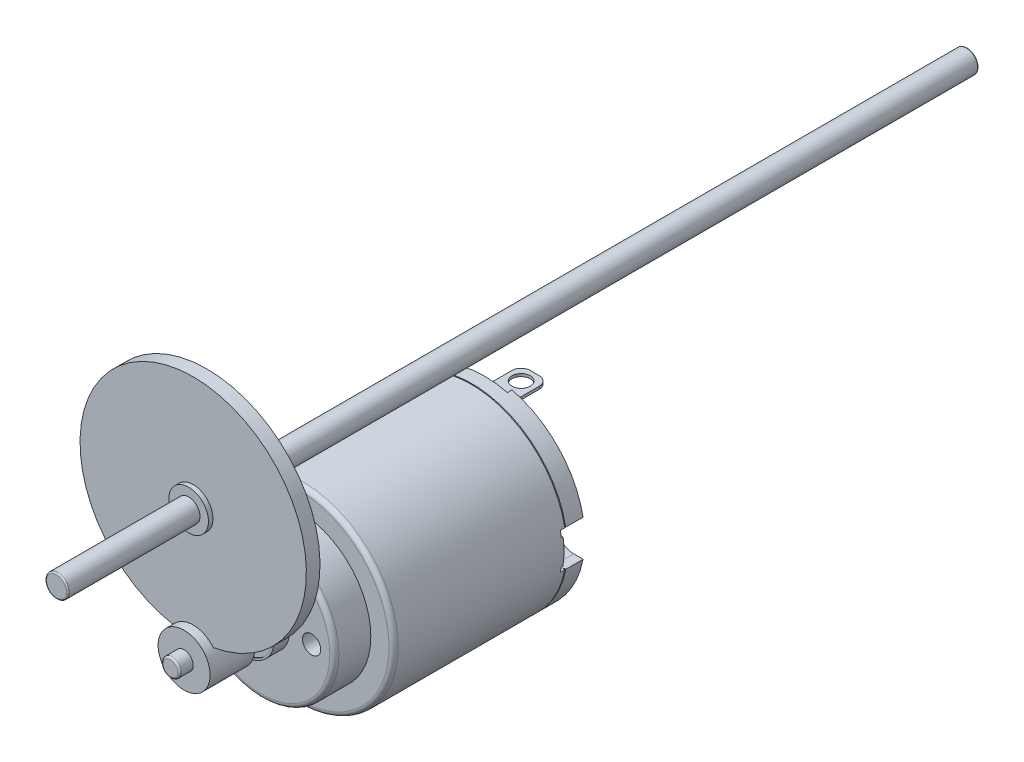
SolidWorks part; units mm, degrees
ref_plane "Plano frontal" through (0, 0, 0) normal (0, 0, 1) x (1, 0, 0)
ref_plane "Plano superior" through (0, 0, 0) normal (0, 1, 0) x (1, 0, 0)
ref_plane "Plano direito" through (0, 0, 0) normal (1, 0, 0) x (0, 0, -1)
sketch "Esboço1" plane through (0, 0, 0) normal (0, 0, 1) x (1, 0, 0)
  circle A0 centre (0, 0) radius 1
  dimension "D1" = 2
extrude "Ressalto-extrusão1" add sketch "Esboço1" along normal blind 38
ref_plane "Plano1" through (0, 0, 28) normal (0, 0, 1) x (1, 0, 0)
sketch "Esboço2" plane through (0, 0, 28) normal (0, 0, 1) x (1, 0, 0)
  circle A0 centre (0, 0) radius 8
  dimension "D1" = 16
extrude "Ressalto-extrusão2" add sketch "Esboço2" against normal blind 25
sketch "Esboço3" plane through (0, 0, 28) normal (0, 0, 1) x (1, 0, 0)
  circle A0 centre (0, 0) radius 3.075
  dimension "D1" = 6.15
extrude "Ressalto-extrusão3" add sketch "Esboço3" along normal blind 1.7
sketch "Esboço4" plane through (0, 0, 3) normal (0, 0, -1) x (-1, 0, 0)
  circle A0 centre (0, 0) radius 10.5
  dimension "D1" = 21
extrude "Ressalto-extrusão4" add sketch "Esboço4" against normal blind 21
sketch "Esboço5" plane through (0, 0, 3) normal (0, 0, -1) x (-1, 0, 0)
  circle A0 centre (0, 0) radius 3.125
  dimension "D1" = 6.25
extrude "Ressalto-extrusão5" add sketch "Esboço5" along normal blind 2
sketch "Esboço6" plane through (0, 0, 3) normal (0, 0, -1) x (-1, 0, 0)
  line L0 (0, 10.5) -> (0, -10.5) construction
  line L2 (1.5, 8.05) -> (-1.5, 8.05)
  line L3 (1.5, 8.05) -> (1.5, 7.75)
  line L4 (1.5, 7.75) -> (-1.5, 7.75)
  line L5 (-1.5, 8.05) -> (-1.5, 7.75)
  line L6 (1.5, 8.05) -> (-1.5, 7.75) construction
  line L7 (1.5, 7.75) -> (-1.5, 8.05) construction
  line L8 (1.5, -7.75) -> (-1.5, -7.75)
  line L9 (1.5, -7.75) -> (1.5, -8.05)
  line L10 (1.5, -8.05) -> (-1.5, -8.05)
  line L11 (-1.5, -7.75) -> (-1.5, -8.05)
  line L12 (1.5, -7.75) -> (-1.5, -8.05) construction
  line L13 (1.5, -8.05) -> (-1.5, -7.75) construction
  circle A0 centre (0, 0) radius 10.5 construction
  point P5 (0, 7.9)
  point P10 (0, -7.9)
  dimension "D1" = 15.5
  dimension "D2" = 0.3
  dimension "D3" = 0.3
  dimension "D4" = 3
  dimension "D5" = 3
  dimension "D6" = 7.75
extrude "Ressalto-extrusão6" add sketch "Esboço6" along normal blind 5
sketch "Esboço7" plane through (0, 8.05, 0) normal (0, 1, 0) x (1, 0, 0)
  line L0 (-1.5, 2) -> (1.5, 2) construction
  circle A0 centre (0, 0.5) radius 1
  dimension "D1" = 2
  dimension "D2" = 1.5
extrude "Corte-extrusão1" cut sketch "Esboço7" against normal blind 4
sketch "Esboço8" plane through (0, -7.75, 0) normal (0, 1, 0) x (1, 0, 0)
  circle A0 centre (0, 0.5) radius 1
extrude "Corte-extrusão2" cut sketch "Esboço8" against normal blind 4
fillet "Filete1" radius 1 4 edges at (1.5, -7.9, -2) (-1.5, -7.9, -2) (1.5, 7.9, -2) (-1.5, 7.9, -2)
fillet "Filete2" radius 0.2 2 edges at (1, 0, 0) (1, 0, 38)
sketch "Esboço9" plane through (0, 0, 3) normal (0, 0, -1) x (-1, 0, 0)
  circle A0 centre (-5.5, 0) radius 1
  circle A1 centre (5.5, 0) radius 1
  dimension "D1" = 11
  dimension "D3" = 2
  dimension "D4" = 2
  dimension "D2" = 5.5
extrude "Corte-extrusão3" cut sketch "Esboço9" against normal blind 38 and the other way blind 15
sketch "Esboço10" plane through (0, 0, 1) normal (0, 0, -1) x (-1, 0, 0)
  line L0 (2.575, 4.4181) -> (2.575, -4.909) construction
  line L2 (2.575, 4.4181) -> (2.575, -4.909)
  line L3 (2.575, -4.909) -> (3.8141, -4.909)
  line L4 (3.8141, -4.909) -> (3.8141, 4.4181)
  line L5 (3.8141, 4.4181) -> (2.575, 4.4181)
extrude "Corte-extrusão4" cut sketch "Esboço10" against normal blind 2
sketch "Esboço11" plane through (0, 0, 3) normal (0, 0, -1) x (-1, 0, 0)
  line L0 (-3.7081, 1.5) -> (-7.3485, 1.5)
  line L1 (7.3485, 1.5) -> (3.7081, 1.5)
  line L3 (7.3485, -1.5) -> (3.7081, -1.5)
  line L5 (-2.5, -7.0711) -> (-2.5, -12.5)
  line L6 (2.5, -7.0711) -> (2.5, -12.5)
  line L7 (-3.7081, -1.5) -> (-7.3485, -1.5)
  line L9 (2.5, 12.5) -> (-2.5, 12.5)
  line L10 (2.5, 12.5) -> (2.5, 7.0711)
  line L11 (2.5, -12.5) -> (-2.5, -12.5)
  line L12 (-2.5, 12.5) -> (-2.5, 7.0711)
  arc A0 (-7.3485, -1.5) -> (-2.5, -7.0711) centre (0, 0) ccw
  circle A1 centre (0, 0) radius 10.5 construction
  arc A2 (-3.7081, -1.5) -> (-2.5, -3.1225) centre (0, 0) ccw
  arc A3 (7.3485, 1.5) -> (2.5, 7.0711) centre (0, 0) ccw
  arc A4 (3.7081, 1.5) -> (2.5, 3.1225) centre (0, 0) ccw
  arc A5 (-2.5, 7.0711) -> (-7.3485, 1.5) centre (0, 0) ccw
  arc A6 (2.5, 3.1225) -> (-3.7081, 1.5) centre (0, 0) ccw
  arc A7 (2.5, -7.0711) -> (7.3485, -1.5) centre (0, 0) ccw
  arc A8 (-2.5, -3.1225) -> (3.7081, -1.5) centre (0, 0) ccw
  point P0 (0, 0)
  dimension "D2" = 3
  dimension "D3" = 8
  dimension "D1" = 5
  dimension "D4" = 25
extrude "Corte-extrusão5" cut sketch "Esboço11" against normal blind 0.5
sketch "Esboço12" plane through (0, 0, 3.5) normal (0, 0, -1) x (-1, 0, 0)
  line L0 (0, 0) -> (0, -6.6243) construction
  line L2 (0, 0) -> (13.3788, 0) construction
  arc A0 (3.375, -5.8457) -> (5.8457, -3.375) centre (0, 0) ccw
  arc A1 (2.375, -4.1136) -> (4.1136, -2.375) centre (0, 0) ccw
  arc A2 (2.375, -4.1136) -> (3.375, -5.8457) centre (2.875, -4.9796) ccw
  arc A3 (4.1136, -2.375) -> (5.8457, -3.375) centre (4.9796, -2.875) cw
  arc A8 (-3.375, 5.8457) -> (-5.8457, 3.375) centre (0, 0) ccw
  arc A9 (-4.1136, 2.375) -> (-5.8457, 3.375) centre (-4.9796, 2.875) cw
  arc A10 (-2.375, 4.1136) -> (-4.1136, 2.375) centre (0, 0) ccw
  arc A11 (-2.375, 4.1136) -> (-3.375, 5.8457) centre (-2.875, 4.9796) ccw
  dimension "D1" = 13.5
  dimension "D2" = 9.5
extrude "Corte-extrusão6" cut sketch "Esboço12" against normal blind 2
sketch "Esboço13" plane through (0, 0, 3) normal (0, 0, 1) x (1, 0, 0)
  line L1 (1.5, 8.05) -> (-1.5, 8.05)
  line L2 (1.5, 8.05) -> (1.5, 7.75)
  line L3 (1.5, 7.75) -> (-1.5, 7.75)
  line L4 (-1.5, 8.05) -> (-1.5, 7.75)
  line L5 (-1.5, -8.05) -> (1.5, -8.05)
  line L6 (-1.5, -8.05) -> (-1.5, -7.75)
  line L7 (-1.5, -7.75) -> (1.5, -7.75)
  line L8 (1.5, -8.05) -> (1.5, -7.75)
extrude "Ressalto-extrusão7" add sketch "Esboço13" along normal blind 6
ref_plane "Plano2" through (0, 0, 5) normal (0, 0, -1) x (-1, 0, 0)
sketch "Esboço14" plane through (0, 0, 5) normal (0, 0, -1) x (-1, 0, 0)
  circle A0 centre (0, 0) radius 11.3093
  circle A1 centre (0, 0) radius 10.3
  arc A2 (-2.5, 10.198) -> (-2.5, -10.198) centre (0, 0) ccw construction
  dimension "D1" = 0.2
extrude "Corte-extrusão7" cut sketch "Esboço14" along normal blind 0.1
fillet "Filete3" radius 0.5 2 edges at (8, 0, 28) (-10.5, 0, 24)
sketch "Esboço15" plane through (0, 0, 29.7) normal (0, 0, 1) x (1, 0, 0)
  circle A0 centre (0, 0) radius 2.875
  circle A1 centre (0, 0) radius 3.075 construction
  dimension "D1" = 0.2
extrude "Corte-extrusão8" cut sketch "Esboço15" against normal blind 0.1
sketch "Esboço16" plane through (0, 0, 3) normal (0, 0, -1) x (-1, 0, 0)
  line L0 (-9.2871, 2) -> (-10.3078, 2)
  line L1 (10.3078, 2) -> (9.2871, 2)
  line L3 (10.3078, -2) -> (9.2871, -2)
  line L7 (-9.2871, -2) -> (-10.3078, -2)
  arc A0 (-2.5, 10.198) -> (-2.5, -10.198) centre (0, 0) ccw construction
  arc A3 (-9.2871, -2) -> (-9.2871, 2) centre (-9.2871, 0) ccw
  arc A4 (9.2871, 2) -> (9.2871, -2) centre (9.2871, 0) ccw
  arc A5 (-10.3078, 2) -> (-10.3078, -2) centre (0, 0) ccw
  arc A6 (10.3078, -2) -> (10.3078, 2) centre (0, 0) ccw
  point P0 (0, 0)
  dimension "D1" = 4
extrude "Corte-extrusão9" cut sketch "Esboço16" against normal blind 2.5
sketch "Esboço17" plane through (0, 0, 5.5) normal (0, 0, -1) x (-1, 0, 0)
  line L0 (-8.5973, 1.3172) -> (-10.417, 1.3172)
  line L1 (10.417, 1.3172) -> (8.5973, 1.3172)
  line L2 (10.417, -1.3172) -> (10.417, -1.5)
  line L3 (10.417, -1.5) -> (8.5666, -1.5)
  line L5 (8.3688, -1.3) -> (8.3951, 1.1172)
  line L6 (10.417, -1.5) -> (10.3928, -1.4965) construction
  line L7 (-8.5973, 1.3172) -> (-8.3951, 1.1172)
  line L8 (-8.3688, -1.3) -> (-8.5666, -1.5)
  line L9 (-8.5666, -1.5) -> (-10.3923, -1.5)
  line L10 (-8.3951, 1.1172) -> (-8.3688, -1.3)
  line L11 (8.5666, -1.5) -> (8.3688, -1.3)
  line L12 (8.5973, 1.3172) -> (8.3951, 1.1172)
  arc A0 (-10.417, 1.3172) -> (-10.3923, -1.5) centre (0, 0) ccw
  arc A2 (10.3923, -1.5) -> (10.417, 1.3172) centre (0, 0) ccw
  point P0 (0, 0)
  point P6 (8.3973, 1.3172)
  point P11 (-8.3973, 1.3172)
  point P13 (-8.3666, -1.5)
  point P14 (8.3666, -1.5)
  arc M6 (-10.3078, 2) -> (-10.3078, -2) centre (0, 0) ccw
extrude "Ressalto-extrusão8" add sketch "Esboço17" along normal blind 0.2 contours L3 A2 L1 L12 L5 L11 | L10 L7 L0 L9 L8 M6 region at (9.4319, -0.0921, 5.5) region at (-9.4319, -0.0921, 5.5)
ref_plane "Plano3" through (0, 0, 36.5) normal (0, 0, 1) x (1, 0, 0)
sketch "Esboço18" plane through (0, 0, 36.5) normal (0, 0, 1) x (1, 0, 0)
  circle A0 centre (0, 0) radius 2.85
  dimension "D1" = 5.7
extrude "Ressalto-extrusão9" add sketch "Esboço18" against normal blind 4.9
ref_plane "Plano4" through (0, 0, 35.5) normal (0, 0, 1) x (1, 0, 0)
sketch "Esboço19" plane through (0, 0, 35.5) normal (0, 0, 1) x (1, 0, 0)
  line L0 (0, 0) -> (0, 14.025) construction
  line L1 (-11.4438, -2.85) -> (12.0372, -2.85) construction
  line L3 (13.7014, 26.45) -> (-10.6901, 26.45) construction
  circle A0 centre (0, 14.025) radius 12.425
  circle A2 centre (0, 0) radius 2.85 construction
  dimension "D1" = 24.85
  dimension "D2" = 29.3
extrude "Ressalto-extrusão10" add sketch "Esboço19" against normal blind 1.5
sketch "Esboço20" plane through (0, 0, 34) normal (0, 0, -1) x (-1, 0, 0)
  circle A0 centre (0, 14.025) radius 2.175
  dimension "D1" = 4.35
extrude "Ressalto-extrusão11" add sketch "Esboço20" against normal blind 2
sketch "Esboço21" plane through (0, 0, 36) normal (0, 0, 1) x (1, 0, 0)
  circle A0 centre (0, 14.025) radius 2.175
extrude "Ressalto-extrusão12" add sketch "Esboço21" against normal blind 3.9
sketch "Esboço22" plane through (0, 0, 32.1) normal (0, 0, -1) x (-1, 0, 0)
  circle A0 centre (0, 14.025) radius 1.25
  dimension "D1" = 2.5
extrude "Corte-extrusão10" cut sketch "Esboço22" against normal blind 7.9 and the other way blind 12
ref_plane "Plano5" through (0, 0, -16.5) normal (0, 0, 1) x (1, 0, 0)
sketch "Esboço23" plane through (0, 0, 35.5) normal (0, 0, 1) x (1, 0, 0)
  circle A0 centre (0, 14.025) radius 1.25
extrude "Ressalto-extrusão13" add sketch "Esboço23" along normal blind 15 and the other way blind 85
fillet "Filete4" radius 0.15 2 edges at (1.25, 14.025, -49.5) (1.25, 14.025, 50.5)
